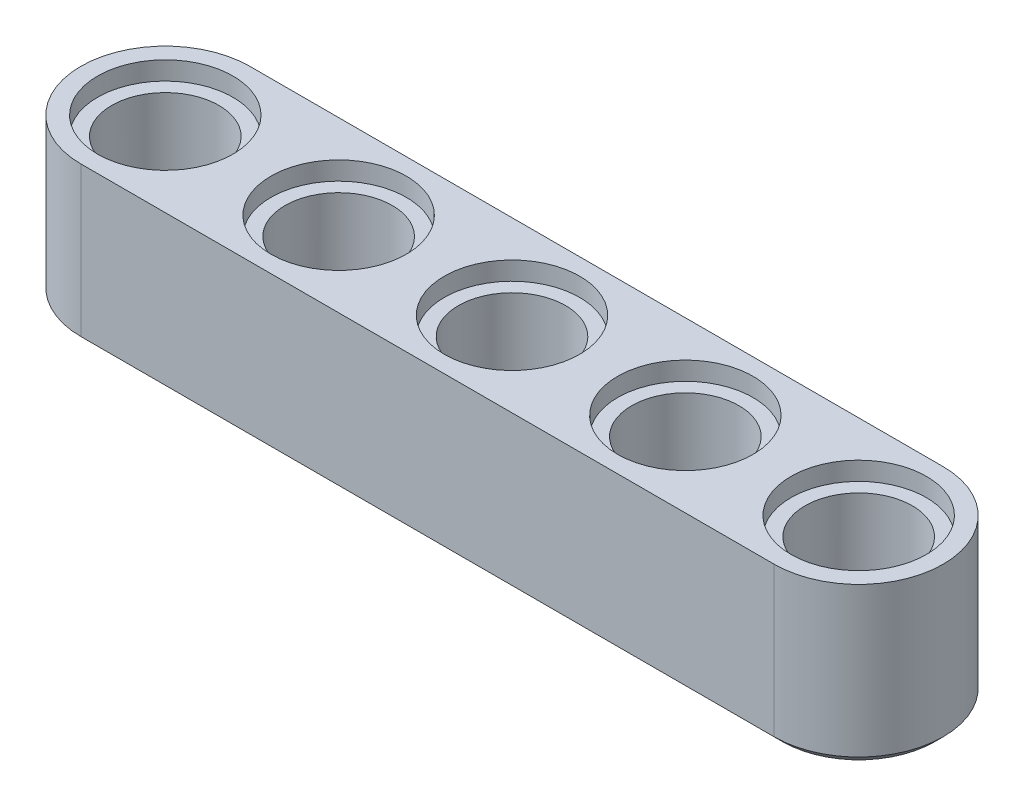
SolidWorks part; units mm, degrees
ref_plane "Front Plane" through (0, 0, 0) normal (0, 0, 1) x (1, 0, 0)
ref_plane "Top Plane" through (0, 0, 0) normal (0, 1, 0) x (1, 0, 0)
ref_plane "Right Plane" through (0, 0, 0) normal (1, 0, 0) x (0, 0, -1)
sketch "Sketch1" plane through (0, 0, 0) normal (0, 1, 0) x (1, 0, 0)
  line L0 (0, 0) -> (32, 0) construction
  line L1 (0, 3.9) -> (32, 3.9)
  line L2 (0, -3.9) -> (32, -3.9)
  arc A0 (0, 3.9) -> (0, -3.9) centre (0, 0) ccw
  arc A1 (32, -3.9) -> (32, 3.9) centre (32, 0) ccw
  point P3 (16, 0)
  dimension "D1" = 32
  dimension "D2" = 7.8
extrude "Boss-Extrude1" add sketch "Sketch1" along normal blind 7.3
sketch "Sketch2" plane through (0, 7.3, 0) normal (0, 1, 0) x (1, 0, 0)
  circle A0 centre (0, 0) radius 2.475
  dimension "D1" = 4.95
extrude "Cut-Extrude1" cut sketch "Sketch2" against normal through all
sketch "Sketch3" plane through (0, 7.3, 0) normal (0, 1, 0) x (1, 0, 0)
  circle A0 centre (0, 0) radius 3.125
  dimension "D1" = 6.25
extrude "Cut-Extrude2" cut sketch "Sketch3" against normal blind 0.85
ref_plane "Plane1" through (0, 3.65, 0) normal (0, 1, 0) x (1, 0, 0)
mirror "Mirror1" about plane through (0, 3.65, 0) normal (0, 1, 0) of "Cut-Extrude2"
pattern_linear "LPattern1" count 5 spacing 8 along (1, 0, 0) of "Cut-Extrude1", "Cut-Extrude2", "Mirror1"
chamfer "Chamfer1" distance 0.4 angle 45 9 edges at (16, 0, 3.9) (35.9, 0, 0) (16, 0, -3.9) (-3.9, 0, 0) (0, 0, 3.125) (8, 0, 3.125) (16, 0, 3.125) (24, 0, 3.125) (32, 0, 3.125)
equation "\"Pitch\"= 8"
equation "\"Beam_Height\"= 7.8"
equation "\"Beam_Width\"= 7.3"
equation "\"Pin_Hole_Dia\"= 4.95"
equation "\"CBore_Dia\"= 6.25"
equation "\"CBore_Depth\"= 0.85"
equation "\"D2@Sketch1\"=\"Beam_Height\""
equation "\"D1@Boss-Extrude1\"=\"Beam_Width\""
equation "\"D1@Sketch2\"=\"Pin_Hole_Dia\""
equation "\"D1@Sketch3\"=\"CBore_Dia\""
equation "\"D1@Cut-Extrude2\"=\"CBore_Depth\""
equation "\"D3@LPattern1\"=\"Pitch\""
